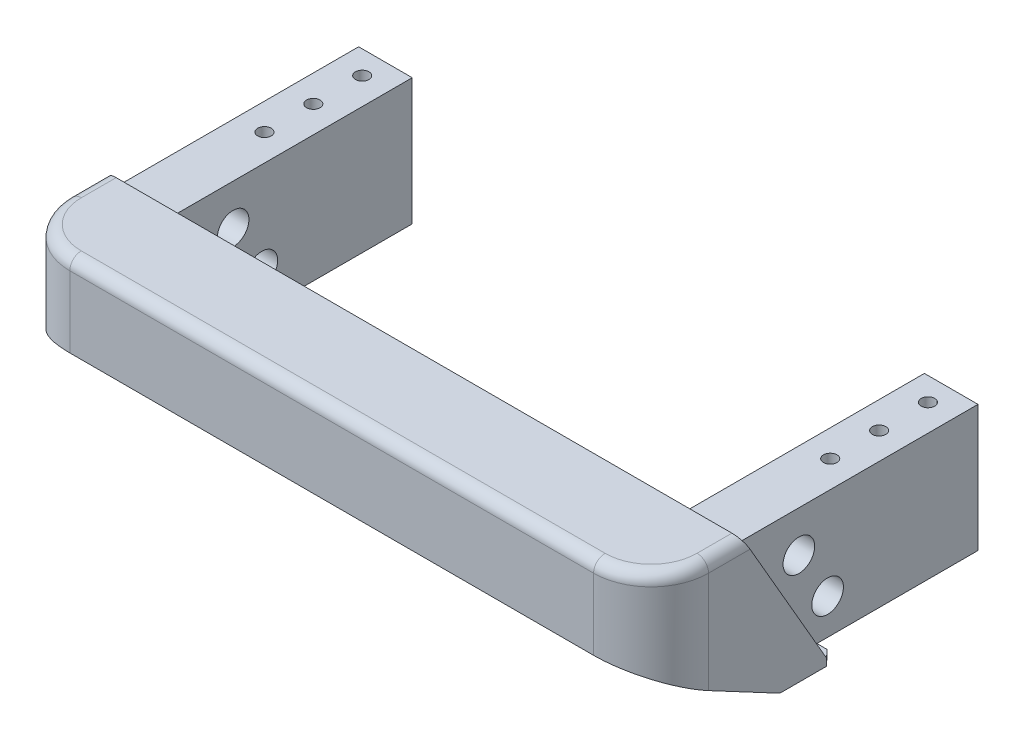
SolidWorks part; units mm, degrees
ref_plane "Front Plane" through (0, 0, 0) normal (0, 0, 1) x (1, 0, 0)
ref_plane "Top Plane" through (0, 0, 0) normal (0, 1, 0) x (1, 0, 0)
ref_plane "Right Plane" through (0, 0, 0) normal (1, 0, 0) x (0, 0, -1)
sketch "Sketch1" plane through (0, 0, 0) normal (1, 0, 0) x (0, 0, -1)
  line L0 (0, 0) -> (0, 50.8)
  line L5 (0, 50.8) -> (29.3294, 0)
  line L6 (29.3294, 0) -> (0, 0)
  dimension "D1" = 60
  dimension "D2" = 50.8
extrude "Boss-Extrude1" add sketch "Sketch1" along normal blind 222.25
sketch "Sketch3" plane through (0, 0, 0) normal (0, 0, 1) x (1, 0, 0)
  line L0 (196.85, 50.8) -> (196.85, 0) construction
  line L1 (218.875, 47.425) -> (200.225, 47.425)
  line L2 (218.875, 47.425) -> (218.875, 3.375)
  line L3 (218.875, 3.375) -> (200.225, 3.375)
  line L4 (200.225, 47.425) -> (200.225, 3.375)
  line L5 (222.25, 50.8) -> (222.25, 0) construction
  line L6 (222.25, 50.8) -> (0, 50.8) construction
  line L7 (222.25, 0) -> (0, 0) construction
  dimension "D1" = 3.375
  dimension "D2" = 3.375
  dimension "D3" = 3.375
  dimension "D4" = 18.65
  dimension "D5" = 25.4
extrude "Boss-Extrude3" add sketch "Sketch3" against normal blind 85 contours L1 L4 L3 L2 region at (209.55, 25.4, 0)
sketch "Sketch15" plane through (0, 47.425, 0) normal (0, 1, 0) x (1, 0, 0)
  circle A0 centre (209.55, 59.9086) radius 2.3495
  circle A1 centre (209.55, 42.9086) radius 2.3495
  circle A2 centre (209.55, 76.9086) radius 2.3495
  dimension "D1" = 4.699
  dimension "D2" = 4.699
  dimension "D3" = 4.699
extrude "Cut-Extrude6" cut sketch "Sketch15" against normal blind 15
sketch "Sketch16" plane through (200.225, 0, 0) normal (-1, 0, 0) x (0, 0, 1)
  circle A0 centre (-22.6727, 33.1173) radius 5.5
  circle A1 centre (-32.6727, 15.7967) radius 5.5
  dimension "D1" = 11
  dimension "D2" = 11
extrude "Cut-Extrude7" cut sketch "Sketch16" against normal through all
ref_plane "Plane1" through (111.125, 0, 0) normal (-1, 0, 0) x (0, 0, 1)
mirror "Mirror1" about plane through (111.125, 0, 0) normal (-1, 0, 0) of "Cut-Extrude7", "Boss-Extrude3", "Cut-Extrude6"
sketch "Sketch4" plane through (222.25, 0, 0) normal (1, 0, 0) x (0, 0, -1)
  line L0 (-5, 50.8) -> (-26.1464, 36.606)
  line L3 (0, 0) -> (0, 50.8)
  line L4 (0, 50.8) -> (-5, 50.8)
  line L5 (0, 0) -> (-5, 0)
  line L6 (-15, 0) -> (-5, 0)
  line L7 (-5, 50.8) -> (-5, 0) construction
  arc A0 (-15, 0) -> (-26.1464, 36.606) centre (-15, 20) cw
  dimension "D2" = 20
  dimension "D1" = 10
  dimension "D3" = 5
extrude "Boss-Extrude4" [suppressed] add sketch "Sketch4" against normal up to surface (222.25 mm away)
sketch "Sketch7" plane through (222.25, 0, 0) normal (1, 0, 0) x (0, 0, -1)
  line L0 (0, 50.8) -> (-32.1286, 50.8)
  line L2 (-32.1286, 22.0436) -> (9.3294, 0)
  line L3 (0, 0) -> (29.3294, 0) construction
  line L4 (9.3294, 0) -> (29.3294, 0)
  line L5 (29.3294, 0) -> (0, 50.8)
  line L8 (-32.1286, 50.8) -> (-32.1286, 22.0436)
  dimension "D1" = 32
  dimension "D2" = 20
  dimension "D3" = 32.1286
extrude "Boss-Extrude5" add sketch "Sketch7" against normal up to surface (222.25 mm away) up to face at (0, 16.9333, -9.7765)
sketch "Sketch8" plane through (222.25, 0, 0) normal (1, 0, 0) x (0, 0, -1)
  line L0 (-32.1286, 22.0436) -> (9.3294, 0) construction
  line L1 (0, 4.9605) -> (9.3294, 0)
  line L2 (0, 4.9605) -> (0, 0)
  line L3 (0, 0) -> (9.3294, 0)
extrude "Cut-Extrude3" cut sketch "Sketch8" against normal up to surface (222.25 mm away) up to face at (0, 21.434, 5.8213)
sketch "Sketch9" plane through (222.25, 0, 0) normal (1, 0, 0) x (0, 0, -1)
  line L0 (29.3294, 0) -> (73.6991, 0) construction
  line L1 (29.3294, 0) -> (29.4449, -0.2)
  line L2 (9.3294, 0) -> (12.6912, -1.7875)
  line L3 (-32.1286, 22.0436) -> (9.3294, 0) construction
  line L4 (29.3294, 0) -> (0, 50.8) construction
  line L5 (29.4449, -0.2) -> (32.5294, -0.2)
  line L6 (32.5294, -0.2) -> (32.5294, -1.7875)
  line L7 (32.5294, -1.7875) -> (12.6912, -1.7875)
  line L8 (9.3294, 0) -> (29.3294, 0) construction
  line L9 (9.3294, 0) -> (29.3294, 0)
  line M9 (9.3294, 0) -> (29.3294, 0)
  dimension "D1" = 0.2
  dimension "D2" = 1.5875
  dimension "D3" = 3.2
extrude "Boss-Extrude6" add sketch "Sketch9" against normal up to surface (222.25 mm away) contours L7 L6 L5 L1 L2 M9 region at (222.25, -0.8833, -21.595) up to face at (0, 24.7287, 5.1197)
sketch "Sketch10" plane through (0, -1.7875, 0) normal (0, -1, 0) x (1, 0, 0)
  line L0 (218.8722, -32.5294) -> (222.25, -28.8294)
  line L1 (0, -32.5294) -> (222.25, -32.5294) construction
  line L2 (222.25, -32.5294) -> (222.25, -12.6912) construction
  line L3 (222.25, -32.5294) -> (218.8722, -32.5294)
  line L4 (222.25, -32.5294) -> (222.25, -28.8294)
  line L6 (111.125, -32.5294) -> (197.8722, -32.5294)
  line L7 (111.125, -32.5294) -> (111.125, -29.4449)
  line L8 (111.125, -29.4449) -> (197.8722, -29.4449)
  line L9 (197.8722, -32.5294) -> (197.8722, -29.4449)
  line L10 (0, -9.2034) -> (222.25, -9.2034) construction
  line L11 (0, 32.1286) -> (0, -12.6912) construction
  line L12 (222.25, 32.1286) -> (222.25, -12.6912) construction
  line L13 (111.125, -9.2034) -> (111.125, -68.2914) construction
  line L14 (0, -29.4449) -> (222.25, -29.4449) construction
  dimension "D1" = 3.3778
  dimension "D2" = 3.7
  dimension "D3" = 21
extrude "Cut-Extrude4" cut sketch "Sketch10" against normal up to next
mirror "Mirror2" about plane through (111.125, 0, 0) normal (-1, 0, 0) of "Cut-Extrude4"
chamfer "Chamfer1" distance 3.5 angle 45 2 edges at (24.3778, -0.9937, -32.5294) (197.8722, -0.9937, -32.5294)
sketch "Sketch11" plane through (0, -1.7875, 0) normal (0, -1, 0) x (1, 0, 0)
  line L0 (111.125, -29.4449) -> (111.125, -11.1659) construction
  line L1 (198.2876, -29.4449) -> (23.9624, -29.4449) construction
  line L2 (0, -12.6912) -> (222.25, -12.6912) construction
  line L3 (66.125, -29.4449) -> (156.125, -29.4449)
  line L4 (66.125, -29.4449) -> (66.125, -12.6912)
  line L5 (66.125, -12.6912) -> (156.125, -12.6912)
  line L6 (156.125, -29.4449) -> (156.125, -12.6912)
  dimension "D1" = 90
extrude "Cut-Extrude5" cut sketch "Sketch11" against normal up to next
fillet "Fillet1" radius 4 1 edges at (111.125, -1.7875, -12.6912) tangent propagation no
fillet "Fillet2" radius 20 2 edges at (0, 36.4218, 32.1286) (222.25, 36.4218, 32.1286)
fillet "Fillet3" radius 4 5 edges at (0, 50.8, 6.0643) (5.8579, 50.8, 26.2708) (222.25, 50.8, 6.0643) (216.3921, 50.8, 26.2708) (111.125, 50.8, 32.1286)
equation "\"Length\"= 222.25"
equation "\"Height\"= 50.8"
equation "\"D2@Sketch1\"=\"Height\""
equation "\"D1@Boss-Extrude1\"=\"Length\""
equation "\"Slot\"= 3.175 + 0.2"
equation "\"D1@Sketch3\"=\"Slot\""
equation "\"D2@Sketch3\"=\"Slot\""
equation "\"D3@Sketch3\"=\"Slot\""
equation "\"Inside_Slot\"= 25.4 - ( 2 * 3.175 ) - ( 2 * 0.2 )"
equation "\"D4@Sketch3\"=\"Inside_Slot\""
